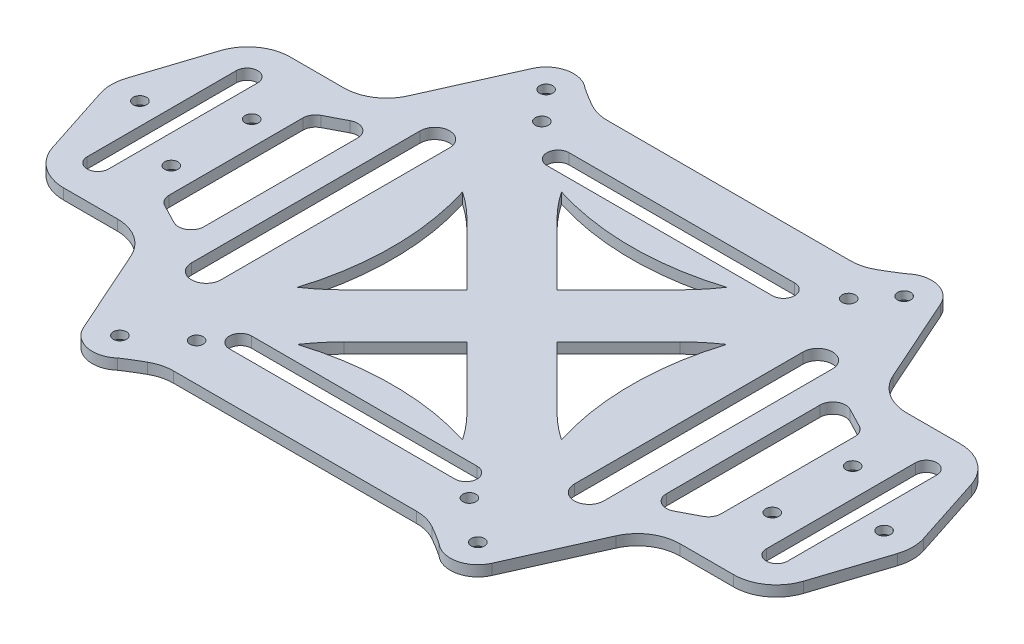
SolidWorks part; units mm, degrees
material "PPS"
ref_plane "前视基准面" through (0, 0, 0) normal (0, 0, 1) x (1, 0, 0)
ref_plane "上视基准面" through (0, 0, 0) normal (0, 1, 0) x (1, 0, 0)
ref_plane "右视基准面" through (0, 0, 0) normal (1, 0, 0) x (0, 0, -1)
sketch "参考" plane through (0, 0, 0) normal (0, 1, 0) x (1, 0, 0)
  line L3 (-133.7177, 0) -> (146.3754, 0) construction
  line L56 (0, 96.0639) -> (0, -115.1457) construction
  line L177 (114.5911, 7.4683) -> (114.5911, -7.4683)
  line L178 (114.5911, 7.4683) -> (43.1936, 17.6463)
  line L179 (114.5911, -7.4683) -> (43.1936, -17.6463)
  line L180 (-114.5911, -7.4683) -> (-43.1936, -17.6463)
  line L181 (-114.5911, 7.4683) -> (-114.5911, -7.4683)
  line L182 (-114.5911, 7.4683) -> (-43.1936, 17.6463)
  arc A18 (-37.7098, 54.831) -> (37.7098, 54.831) centre (0, 111.5317) ccw
  arc A20 (48.2756, 48.4632) -> (43.1936, 17.6463) centre (246.1791, 0) ccw
  arc A21 (48.2756, 48.4632) -> (37.7098, 54.831) centre (42, 50) ccw
  arc A22 (-37.7098, -54.831) -> (37.7098, -54.831) centre (0, -111.5317) cw
  arc A23 (48.2756, -48.4632) -> (43.1936, -17.6463) centre (246.1791, 0) cw
  arc A24 (48.2756, -48.4632) -> (37.7098, -54.831) centre (42, -50) cw
  arc A26 (-48.2756, -48.4632) -> (-37.7098, -54.831) centre (-42, -50) ccw
  arc A27 (-48.2756, -48.4632) -> (-43.1936, -17.6463) centre (-246.1791, 0) ccw
  arc A28 (-48.2756, 48.4632) -> (-37.7098, 54.831) centre (-42, 50) cw
  arc A30 (-48.2756, 48.4632) -> (-43.1936, 17.6463) centre (-246.1791, 0) cw
  dimension "D11" = 50
  dimension "D12" = 42
sketch "草图1" plane through (0, 0, 0) normal (0, 1, 0) x (1, 0, 0)
  line L0 (-160.1541, 0) -> (172.3115, 0) construction
  line L1 (0, 124.2182) -> (0, -143.4382) construction
  line L2 (79.6696, -17.5) -> (79.6696, 17.5) construction
  line L3 (77.1696, -17.5) -> (77.1696, 17.5)
  line L4 (82.1696, -17.5) -> (82.1696, 17.5)
  line L5 (-133.7177, 0) -> (146.3754, 0) construction
  line L6 (47.9, 52.6334) -> (59.525, 26.5883)
  line L7 (59.525, 26.5883) -> (85.8696, 26.5883)
  line L8 (85.8696, 26.5883) -> (94.5058, 0)
  line L9 (59.525, -26.5883) -> (85.8696, -26.5883)
  line L10 (47.9, -52.6334) -> (59.525, -26.5883)
  line L11 (85.8696, -26.5883) -> (94.5058, 0)
  line L12 (-47.9, -52.6334) -> (-59.525, -26.5883)
  line L13 (-59.525, -26.5883) -> (-85.8696, -26.5883)
  line L14 (-85.8696, -26.5883) -> (-94.5058, 0)
  line L15 (-85.8696, 26.5883) -> (-94.5058, 0)
  line L16 (-47.9, 52.6334) -> (-59.525, 26.5883)
  line L17 (-59.525, 26.5883) -> (-85.8696, 26.5883)
  line L18 (-79.6696, -17.5) -> (-79.6696, 17.5) construction
  line L19 (-77.1696, -17.5) -> (-77.1696, 17.5)
  line L20 (-82.1696, -17.5) -> (-82.1696, 17.5)
  line L21 (-24.996, 14.4296) -> (-10.5664, 0)
  line L22 (14.4296, 24.996) -> (0, 10.5664)
  line L23 (-24.996, -14.4296) -> (-10.5664, 0)
  line L24 (-14.4296, 24.996) -> (0, 10.5664)
  line L25 (0, 96.0639) -> (0, -115.1457) construction
  line L26 (24.996, -14.4296) -> (10.5664, 0)
  line L27 (24.996, 14.4296) -> (10.5664, 0)
  line L28 (-14.4296, -24.996) -> (0, -10.5664)
  line L29 (14.4296, -24.996) -> (0, -10.5664)
  line L30 (44.9192, -26.8293) -> (44.9192, 26.8293) construction
  line L31 (41.4687, -26.8293) -> (41.4687, 26.8293)
  line L32 (48.3697, -26.8293) -> (48.3697, 26.8293)
  line L33 (-26.4535, -37.2441) -> (26.4535, -37.2441) construction
  line L34 (-26.4535, -34.637) -> (26.4535, -34.637)
  line L35 (-26.4535, -39.8513) -> (26.4535, -39.8513)
  line L36 (-26.4535, 37.2441) -> (26.4535, 37.2441) construction
  line L37 (-26.4535, 34.637) -> (26.4535, 34.637)
  line L38 (-26.4535, 39.8513) -> (26.4535, 39.8513)
  line L39 (-44.9192, -26.8293) -> (-44.9192, 26.8293) construction
  line L40 (-41.4687, -26.8293) -> (-41.4687, 26.8293)
  line L41 (-48.3697, -26.8293) -> (-48.3697, 26.8293)
  line L42 (-30.9782, 50.8906) -> (30.9782, 50.8906)
  line L43 (-30.9782, -50.8906) -> (30.9782, -50.8906)
  circle A6 centre (42, 50) radius 1.55
  circle A7 centre (42, -50) radius 1.55
  circle A8 centre (-42, -50) radius 1.55
  circle A9 centre (-42, 50) radius 1.55
  circle A10 centre (36, 43) radius 1.55
  circle A11 centre (32, -42) radius 1.55
  circle A12 centre (-32, -42) radius 1.55
  circle A13 centre (-36, 43) radius 1.55
  arc A14 (47.9, 52.6334) -> (37.7098, 54.831) centre (42, 50) ccw
  arc A15 (-37.7098, 54.831) -> (-30.9782, 50.8906) centre (0, 111.5317) ccw
  arc A18 (77.1696, -17.5) -> (82.1696, -17.5) centre (79.6696, -17.5) ccw
  arc A19 (82.1696, 17.5) -> (77.1696, 17.5) centre (79.6696, 17.5) ccw
  circle A20 centre (70.5, 9.4358) radius 1.55
  circle A21 centre (70.5, -9.4358) radius 1.55
  circle A22 centre (-70.5, -9.4358) radius 1.55
  circle A23 centre (-70.5, 9.4358) radius 1.55
  circle A24 centre (87.3, 0) radius 1.55
  arc A25 (48.2756, 48.4632) -> (37.7098, 54.831) centre (42, 50) ccw construction
  arc A26 (47.9, -52.6334) -> (37.7098, -54.831) centre (42, -50) cw
  arc A27 (-37.7098, -54.831) -> (-30.9782, -50.8906) centre (0, -111.5317) cw
  arc A28 (-47.9, 52.6334) -> (-37.7098, 54.831) centre (-42, 50) cw
  arc A29 (-77.1696, -17.5) -> (-82.1696, -17.5) centre (-79.6696, -17.5) cw
  arc A30 (-82.1696, 17.5) -> (-77.1696, 17.5) centre (-79.6696, 17.5) cw
  circle A31 centre (-87.3, 0) radius 1.55
  arc A32 (-47.9, -52.6334) -> (-37.7098, -54.831) centre (-42, -50) ccw
  arc A33 (-24.996, 14.4296) -> (-30.9782, 19.3706) centre (-53.9062, -14.4807) ccw
  arc A34 (-24.996, -14.4296) -> (-30.9782, -19.3706) centre (-53.9062, 14.4807) cw
  arc A35 (-30.9782, -19.3706) -> (-30.9782, 19.3706) centre (-93.0146, 0) ccw
  arc A36 (-14.4296, 24.996) -> (-19.3706, 30.9782) centre (14.4807, 53.9062) cw
  arc A37 (-19.3706, 30.9782) -> (19.3706, 30.9782) centre (0, 93.0146) ccw
  arc A38 (14.4296, 24.996) -> (19.3706, 30.9782) centre (-14.4807, 53.9062) ccw
  arc A39 (24.996, 14.4296) -> (30.9782, 19.3706) centre (53.9062, -14.4807) cw
  arc A40 (30.9782, 19.3706) -> (30.9782, -19.3706) centre (93.0146, 0) ccw
  arc A41 (24.996, -14.4296) -> (30.9782, -19.3706) centre (53.9062, 14.4807) ccw
  arc A42 (14.4296, -24.996) -> (19.3706, -30.9782) centre (-14.4807, -53.9062) cw
  arc A43 (19.3706, -30.9782) -> (-19.3706, -30.9782) centre (0, -93.0146) ccw
  arc A44 (-14.4296, -24.996) -> (-19.3706, -30.9782) centre (14.4807, -53.9062) ccw
  arc A45 (41.4687, -26.8293) -> (48.3697, -26.8293) centre (44.9192, -26.8293) ccw
  arc A46 (48.3697, 26.8293) -> (41.4687, 26.8293) centre (44.9192, 26.8293) ccw
  arc A47 (-26.4535, -34.637) -> (-26.4535, -39.8513) centre (-26.4535, -37.2441) ccw
  arc A48 (26.4535, -39.8513) -> (26.4535, -34.637) centre (26.4535, -37.2441) ccw
  arc A49 (-26.4535, 34.637) -> (-26.4535, 39.8513) centre (-26.4535, 37.2441) cw
  arc A50 (26.4535, 39.8513) -> (26.4535, 34.637) centre (26.4535, 37.2441) cw
  arc A51 (-41.4687, -26.8293) -> (-48.3697, -26.8293) centre (-44.9192, -26.8293) cw
  arc A52 (-48.3697, 26.8293) -> (-41.4687, 26.8293) centre (-44.9192, 26.8293) cw
  arc A53 (30.9782, 50.8906) -> (37.7098, 54.831) centre (0, 111.5317) ccw
  arc A54 (30.9782, -50.8906) -> (37.7098, -54.831) centre (0, -111.5317) cw
  point P30 (79.6696, 0)
  point P63 (44.9192, 0)
  point P78 (-79.6696, 0)
  point P98 (0, 0)
  point P116 (0, -37.2441)
  point P129 (0, 37.2441)
  point P136 (-44.9192, 0)
  dimension "D1" = 50
  dimension "D3" = 3.1
  dimension "D8" = 2.5
  dimension "D10" = 3.1
  dimension "D12" = 3.1
  dimension "D2" = 42
  dimension "D4" = 36
  dimension "D5" = 32
  dimension "D6" = 42
  dimension "D7" = 43
  dimension "D9" = 35
  dimension "D11" = 70.5
  dimension "D13" = 87.3
  dimension "D14" = 4
extrude "凸台-拉伸1" add sketch "草图1" along normal blind 2.5
fillet "圆角1" radius 10 14 edges at (59.525, 1.25, -26.5883) (85.8696, 1.25, -26.5883) (85.8696, 1.25, 26.5883) (94.5058, 1.25, 0) (59.525, 1.25, 26.5883) (-59.525, 1.25, 26.5883) (-59.525, 1.25, -26.5883) (-85.8696, 1.25, -26.5883) (-85.8696, 1.25, 26.5883) (-94.5058, 1.25, 0) (30.9782, 1.25, -50.8906) (-30.9782, 1.25, -50.8906) (30.9782, 1.25, 50.8906) (-30.9782, 1.25, 50.8906)
chamfer "倒角2" distance 0.615 angle 30 10 edges at (-70.5, 0, 10.9858) (-70.5, 0, -10.9858) (70.5, 0, 7.8858) (70.5, 0, -7.8858) (-87.3, 0, -1.55) (87.3, 0, 1.55) (-42, 0, 51.55) (42, 0, 48.45) (-42, 0, -51.55) (42, 0, -48.45) first distance on face at (-70.5, 2.5, 10.9858) first distance on face at (-70.5, 2.5, -10.9858) first distance on face at (70.5, 2.5, 7.8858) first distance on face at (70.5, 2.5, -7.8858) first distance on face at (-87.3, 2.5, -1.55) first distance on face at (87.3, 2.5, 1.55) first distance on face at (-42, 2.5, 51.55) first distance on face at (42, 2.5, 48.45) first distance on face at (-42, 2.5, -51.55) first distance on face at (42, 2.5, -48.45)
sketch "减重草图镂空-如果影响结构强度则取消" plane through (0, 0, 0) normal (0, -1, 0) x (1, 0, 0)
  line L0 (0, 0) -> (0, 77.9145) construction
  line L1 (0, 0) -> (127.571, 0) construction
  line L2 (-64.75, 17.5) -> (-54.25, 22.966)
  line L3 (-54.25, 22.966) -> (-54.25, -22.966)
  line L4 (-54.25, -22.966) -> (-64.75, -17.5)
  line L5 (-64.75, -17.5) -> (-64.75, 17.5)
  line L6 (54.25, -22.966) -> (64.75, -17.5)
  line L7 (54.25, 22.966) -> (54.25, -22.966)
  line L8 (64.75, 17.5) -> (54.25, 22.966)
  line L9 (64.75, -17.5) -> (64.75, 17.5)
  circle A1 centre (-70.5, 9.4358) radius 1.55 construction
  dimension "D1" = 5.75
  dimension "D2" = 54.25
  dimension "D3" = 62.5
  dimension "D4" = 17.5
extrude "减重-如果影响结构强度则取消" cut sketch "减重草图镂空-如果影响结构强度则取消" against normal through all
fillet "圆角2" radius 3 8 edges at (64.75, 1.25, 17.5) (64.75, 1.25, -17.5) (54.25, 1.25, -22.966) (54.25, 1.25, 22.966) (-54.25, 1.25, -22.966) (-64.75, 1.25, -17.5) (-64.75, 1.25, 17.5) (-54.25, 1.25, 22.966)
